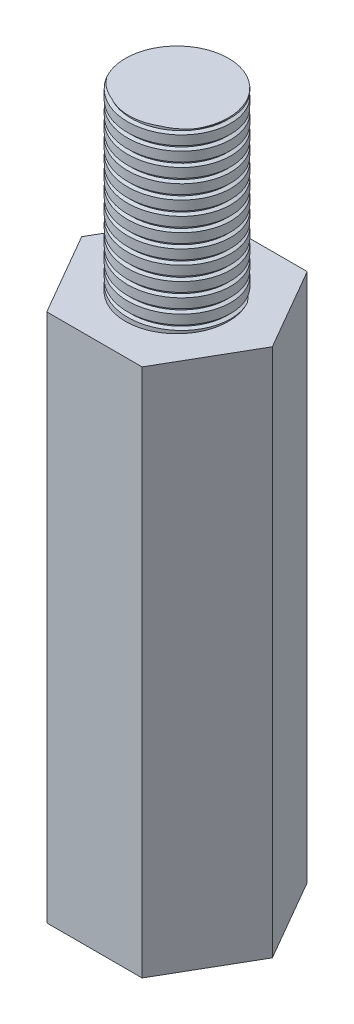
SolidWorks part; units mm, degrees
note: The reader was unsure of these and kept them because the rebuilt part matched: shared geometry of "草图1<3>".
ref_plane "前视基准面" through (0, 0, 0) normal (0, 0, 1) x (1, 0, 0)
ref_plane "上视基准面" through (0, 0, 0) normal (0, 1, 0) x (1, 0, 0)
ref_plane "右视基准面" through (0, 0, 0) normal (1, 0, 0) x (0, 0, -1)
sketch "草图1" plane through (0, 0, 0) normal (0, 1, 0) x (1, 0, 0)
  line L0 (0, 0) -> (0, 4.5761) construction
  line L1 (1.351, -2.34) -> (2.702, 0)
  line L2 (2.702, 0) -> (1.351, 2.34)
  line L3 (1.351, 2.34) -> (-1.351, 2.34)
  line L4 (-1.351, 2.34) -> (-2.702, 0)
  line L5 (-2.702, 0) -> (-1.351, -2.34)
  line L6 (-1.351, -2.34) -> (1.351, -2.34)
  line L7 (0, 4.5761) -> (0, -3.6794) construction
  circle A0 centre (0, 0) radius 2.34 construction
  circle A1 centre (0, 0) radius 1.46
  dimension "D1" = 4.68
  dimension "D2" = 2.92
extrude "凸台-拉伸1" add sketch "草图1" along normal blind 15 contours A1 | L5 L6 L1 L2 L3 L4 A1
extrude "切除-拉伸1" cut sketch "草图1<3>" along normal blind 5 contours A1
sketch "草图1<3>" plane through (0, 0, 0) normal (0, 1, 0) x (1, 0, 0) same geometry as "草图1"
sketch "草图2" plane through (0, 15, 0) normal (0, 1, 0) x (1, 0, 0)
  circle A0 centre (0, 0) radius 1.46
  dimension "D1" = 2.92
extrude "凸台-拉伸2" add sketch "草图2" along normal blind 5 separate body
ref_plane "基准面1" through (0, 0, 0) normal (0, 0, -1) x (-1, 0, 0)
sketch "草图4" plane through (0, 0, 0) normal (0, 0, -1) x (-1, 0, 0)
  line L0 (0, 0) -> (0, 28.5702) construction
  line L1 (-1.56, 15) -> (-1.56, 15.2)
  line L2 (-1.56, 15.2) -> (-1.36, 15.1333)
  line L3 (-1.36, 15.0667) -> (-1.56, 15)
  line L4 (-1.26, 15.1) -> (-2.0659, 15.1) construction
  line L5 (-2.0659, 15.1) -> (-0.8933, 15.1) construction
  line L7 (-1.46, 20) -> (-1.46, 15) construction
  line L8 (-1.36, 15.1333) -> (-1.36, 15.0667)
  line L9 (-1.46, 15) -> (1.46, 15) construction
  point P14 (0, 0)
  point P15 (0, 0)
  dimension "D1" = 0.1
  dimension "D2" = 0.1
  dimension "D3" = 0.1
  dimension "D4" = 0.3
  dimension "D5" = 0.2
  dimension "D6" = 0.1
  dimension "D7" = 0.0667
  dimension "D8" = 0.0667
ref_plane "基准面2" through (0, 15.1, 0) normal (0, 1, 0) x (1, 0, 0)
sketch "草图5" plane through (0, 15.1, 0) normal (0, 1, 0) x (1, 0, 0)
  circle A0 centre (0, 0) radius 1.46
  dimension "D1" = 2.92
curve "螺旋线/涡状线1" pitch 0.4 height 7.5 turns 18.75
sweep "切除-扫描1" cut profiles "草图4" path "螺旋线/涡状线1"
sketch "草图6" plane through (0, 0, 0) normal (0, -1, 0) x (1, 0, 0)
  circle A0 centre (0, 0) radius 1.46
curve "螺旋线/涡状线2" pitch 0.4 height 9.5 turns 23.75
sketch "草图7" plane through (0, 0, 0) normal (0, 0, -1) x (-1, 0, 0)
  line L0 (1.46, 0.2) -> (1.66, 0.1333)
  line L1 (1.66, 0.0667) -> (1.46, 0)
  line L2 (1.46, 0.2) -> (1.46, 0)
  line L3 (1.66, 0.1333) -> (1.66, 0.0667)
  line L8 (1.351, 0) -> (-1.351, 0) construction
  dimension "D1" = 0.2
  dimension "D3" = 1.46
  dimension "D4" = 0.2
sweep "切除-扫描2" cut profiles "草图7" path "螺旋线/涡状线2"
equation "\"chang\"= 20mm"
equation "\"r\"= 2.92mm"
equation "\"luowengao\"= 6.5mm"
equation "\"rr\"= 4.68mm"
equation "\"D1@草图1\"=\"rr\""
equation "\"D2@草图1\"=\"r\""
equation "\"D1@凸台-拉伸1\"=\"chang\""
equation "\"D1@切除-拉伸1\"=\"luowengao\"+5mm"
equation "\"D1@草图2\"=\"r\""
equation "\"D1@凸台-拉伸2\"=\"luowengao\""
